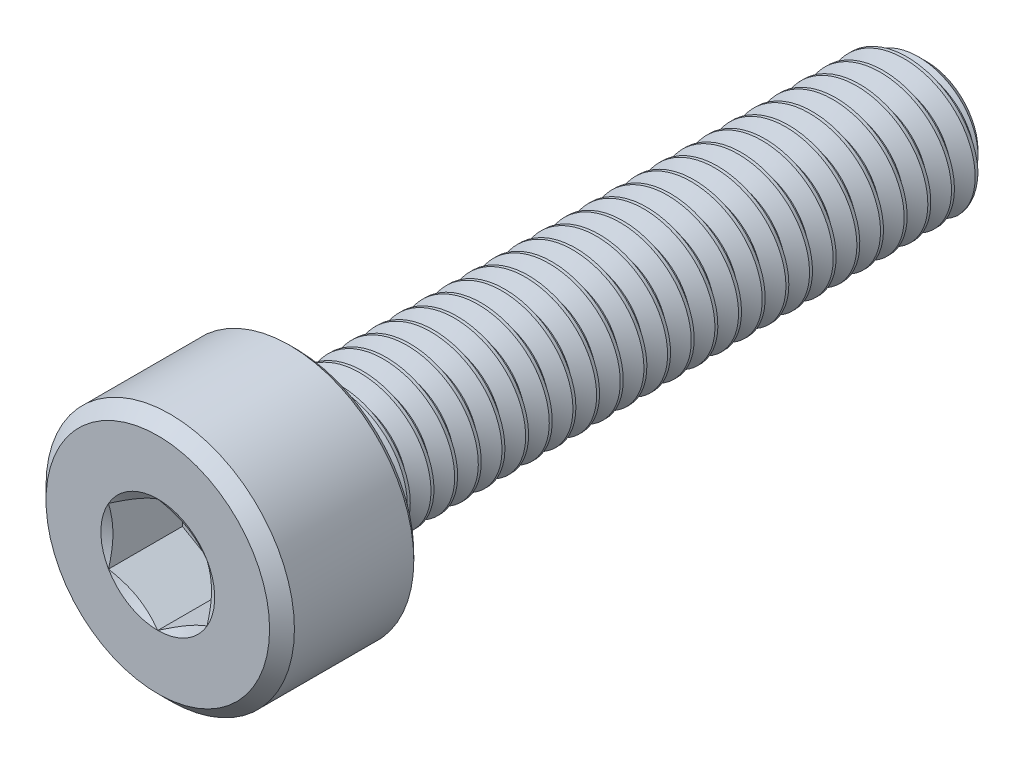
SolidWorks part; units mm, degrees
ref_plane "Front Plane" through (0, 0, 0) normal (0, 0, 1) x (1, 0, 0)
ref_plane "Top Plane" through (0, 0, 0) normal (0, 1, 0) x (1, 0, 0)
ref_plane "Right Plane" through (0, 0, 0) normal (1, 0, 0) x (0, 0, -1)
sketch "Sketch1" plane through (0, 0, 0) normal (1, 0, 0) x (0, 0, -1)
  line L0 (9.75, 0) -> (-9.75, 0) construction
  line L1 (-9.75, 0) -> (-9.75, 3.15) construction
  line L2 (-6.25, 1.75) -> (-6.25, 0) construction
  line L3 (9.15, 0) -> (9.15, 0.6) construction
  line L4 (-6.25, 0) -> (-6.25, -1.75) construction
  point P6 (-9.75, -1.25)
  point P9 (-9.75, 1.25)
  point P10 (8.25, -1.75)
  dimension "D1" = 0.6
  dimension "D2" = 1.5
sketch "Sketch2" plane through (0, 0, 0) normal (1, 0, 0) x (0, 0, -1)
  line L0 (9.75, 1.3) -> (9.3, 1.75)
  line L1 (-9.75, 3.15) -> (-6.25, 3.15)
  line L2 (-9.75, 3.15) -> (-9.75, 0)
  line L4 (-6.25, 3.15) -> (-6.25, 1.75)
  line L5 (-6.25, 1.75) -> (9.3, 1.75)
  line L8 (9.75, 1.3) -> (9.75, 0)
  line L9 (9.75, 0) -> (-9.75, 0) construction
  line L10 (9.75, 0) -> (-9.75, 0)
  dimension "D1" = 135
  dimension "D2" = 0.45
revolve "Revolve1" add sketch "Sketch2" angle 360 about L10
sketch "Sketch4" plane through (0, 0, 9.75) normal (0, 0, 1) x (1, 0, 0)
  line L1 (0, 1.4434) -> (-1.25, 0.7217)
  line L2 (-1.25, 0.7217) -> (-1.25, -0.7217)
  line L3 (-1.25, -0.7217) -> (0, -1.4434)
  line L4 (0, -1.4434) -> (1.25, -0.7217)
  line L5 (1.25, -0.7217) -> (1.25, 0.7217)
  line L6 (1.25, 0.7217) -> (0, 1.4434)
  circle A0 centre (0, 0) radius 1.25 construction
  circle A1 centre (0, 0) radius 3.15 construction
  circle A2 centre (0, 0) radius 3.15 construction
  dimension "D1" = 2.5
extrude "Cut-Extrude1" cut sketch "Sketch4" against normal blind 1.875
sketch "Sketch5" plane through (0, 0, 9.75) normal (0, 0, 1) x (1, 0, 0)
  circle A0 centre (0, 0) radius 1.4434
extrude "Cut-Extrude2" cut sketch "Sketch5" against normal blind 10 draft 60
chamfer "Chamfer1" distance 0.315 angle 45 1 edges at (-3.15, 0, 9.75)
chamfer "Chamfer2" distance 0.1575 angle 45 1 edges at (-3.15, 0, 6.25)
sketch "Sketch3" plane through (0, 0, -9.75) normal (0, 0, -1) x (-1, 0, 0)
  circle A0 centre (0, 0) radius 1.75 construction
  circle A1 centre (0, 0) radius 1.75
curve "Helix/Spiral1" pitch 0.6 height 16.3 turns 27.1667
sketch "Sketch7" plane through (0, 0, 0) normal (1, 0, 0) x (0, 0, -1)
  line L0 (9.7125, 1.815) -> (10.0125, 1.2953) construction
  line L1 (10.0125, 1.2953) -> (10.3125, 1.815) construction
  line L2 (10.3125, 1.815) -> (9.7125, 1.815) construction
  line L3 (9.75, 1.75) -> (10.275, 1.75)
  line L4 (10.0125, 1.815) -> (10.0125, 1.75) construction
  line L5 (10.0125, 1.75) -> (10.0125, 1.3603) construction
  line L6 (10.0125, 1.3603) -> (10.0125, 1.2953) construction
  line L7 (9.975, 1.3603) -> (10.05, 1.3603)
  line L8 (9.7313, 1.7825) -> (10.2938, 1.7825) construction
  line L9 (10.05, 1.3603) -> (10.275, 1.75)
  line L10 (9.975, 1.3603) -> (9.75, 1.75)
  point P0 (10.0125, 1.7825)
  dimension "D1" = 0.6
  dimension "D2" = 0.075
sweep "Cut-Sweep1" cut profiles "Sketch7" path "Helix/Spiral1"
sketch "Sketch8" plane through (0, 0, 0) normal (1, 0, 0) x (0, 0, -1)
  line L0 (-7.875, 0) -> (-7.875, 1.7825)
  line L1 (-7.875, -0.7217) -> (-7.875, 0.7217) construction
  line L2 (-7.875, 1.7825) -> (-5.95, 1.7825)
  line L3 (-5.95, 1.7825) -> (-4.9209, 0)
  line L4 (-4.9209, 0) -> (-7.875, 0)
  line L5 (9.75, 0) -> (-9.75, 0) construction
  line L6 (-6.25, -2.9925) -> (-6.25, 2.9925) construction
  line L9 (9.7313, 1.7825) -> (10.2938, 1.7825) construction
  dimension "D1" = 60
  dimension "D2" = 0.3
revolve "Revolve2" add sketch "Sketch8" angle 360 about L4
equation "\"D1@Sketch1\" = \"Thread Pitch@Sketch1\""
equation "\"D2@Sketch2\"=\"D1@Sketch1\"*.75"
equation "\"D4@Helix/Spiral1\" = \"Thread Pitch@Sketch1\""
equation "\"D3@Helix/Spiral1\"=\"Length@Sketch1\" + (\"Thread Pitch@Sketch1\"*0.5)"
equation "\"D1@Sketch4\"=\"drive Size@Sketch1\""
equation "\"D1@Cut-Extrude1\"=\"D1@Sketch4\"*.75"
equation "\"D19\"= \"D1@Sketch4\" * .75"
equation "\"D1@Chamfer1\" = \"Head Diameter@Sketch1\" * .05"
equation "\"D1@Chamfer2\"=\"D1@Chamfer1\"/2"
equation "\"D2@Sketch7\"=\"D1@Sketch7\"/8"
equation "\"D1@Sketch7\"=\"D4@Helix/Spiral1\""
equation "\"D2@Sketch1\" = \"Thread Pitch@Sketch1\" * 2.5"
equation "\"D2@Sketch8\"=\"Thread Pitch@Sketch1\"*0.5"
